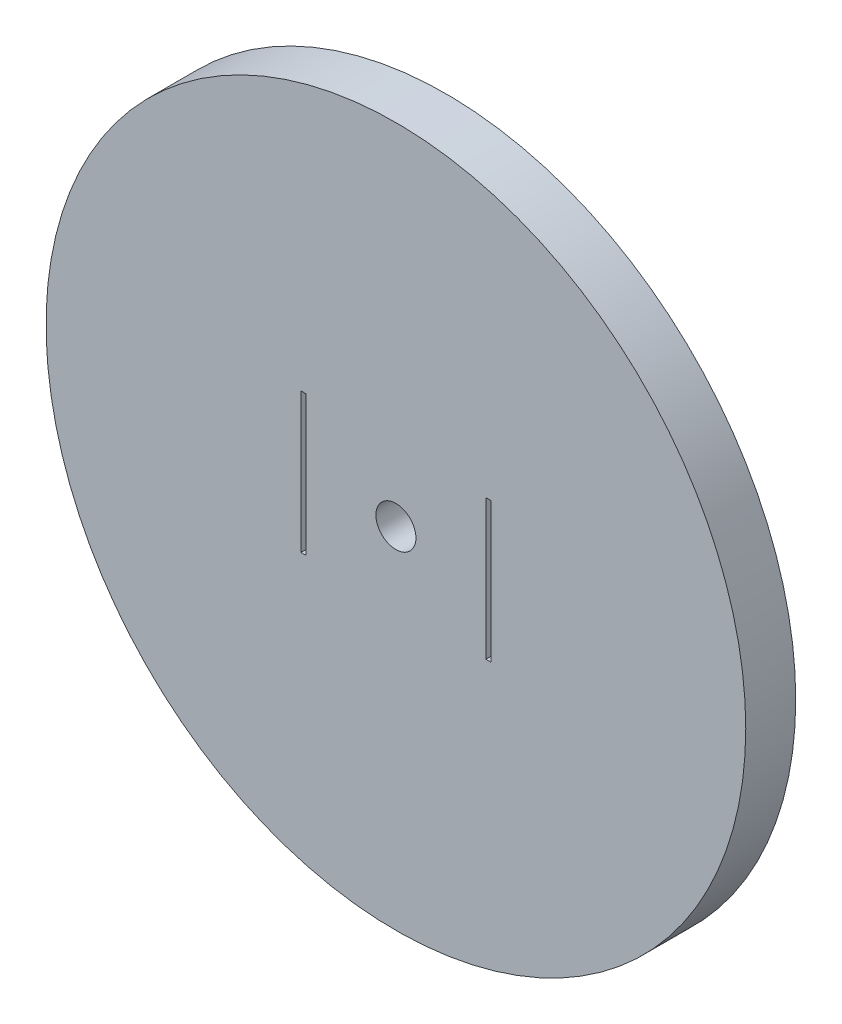
SolidWorks part; units mm, degrees
ref_plane "Front Plane" through (0, 0, 0) normal (0, 0, 1) x (1, 0, 0)
ref_plane "Top Plane" through (0, 0, 0) normal (0, 1, 0) x (1, 0, 0)
ref_plane "Right Plane" through (0, 0, 0) normal (1, 0, 0) x (0, 0, -1)
sketch "Sketch1" plane through (0, 0, 0) normal (0, 0, 1) x (1, 0, 0)
  line L0 (0, 10.3237) -> (0, -11.9962) construction
  line L1 (-9.5, 7) -> (-9, 7)
  line L2 (-9.5, 7) -> (-9.5, -7)
  line L3 (-9.5, -7) -> (-9, -7)
  line L4 (-9, 7) -> (-9, -7)
  line L5 (9, 7) -> (9, -7)
  line L6 (9.5, -7) -> (9, -7)
  line L7 (9.5, 7) -> (9.5, -7)
  line L8 (9.5, 7) -> (9, 7)
  circle A0 centre (0, 0) radius 35
  circle A1 centre (0, 0) radius 2
  dimension "D1" = 4
  dimension "D2" = 70
  dimension "D3" = 0.5
  dimension "D4" = 9
  dimension "D5" = 7
  dimension "D6" = 7
extrude "Boss-Extrude1" add sketch "Sketch1" along normal blind 5
sketch "Sketch3" plane through (0, 0, 0) normal (0, 1, 0) x (1, 0, 0)
  line L0 (-24, 14.6321) -> (-24, 0) construction
  line L1 (35, 0) -> (-35, 0) construction
  line L2 (-28.35, 14.6321) -> (-28.35, 0)
  line L3 (-28.35, 0) -> (-24, 0)
  line L4 (-24, 0) -> (-24, 18.9821)
  line L5 (-35, 0) -> (-35, -5) construction
  circle A0 centre (-24, 14.6321) radius 4.35 construction
  arc A1 (-28.35, 14.6321) -> (-24, 18.9821) centre (-24, 14.6321) cw
  dimension "D1" = 8.7
  dimension "D2" = 11
revolve "Revolve1" add sketch "Sketch3" angle 360 about L0
